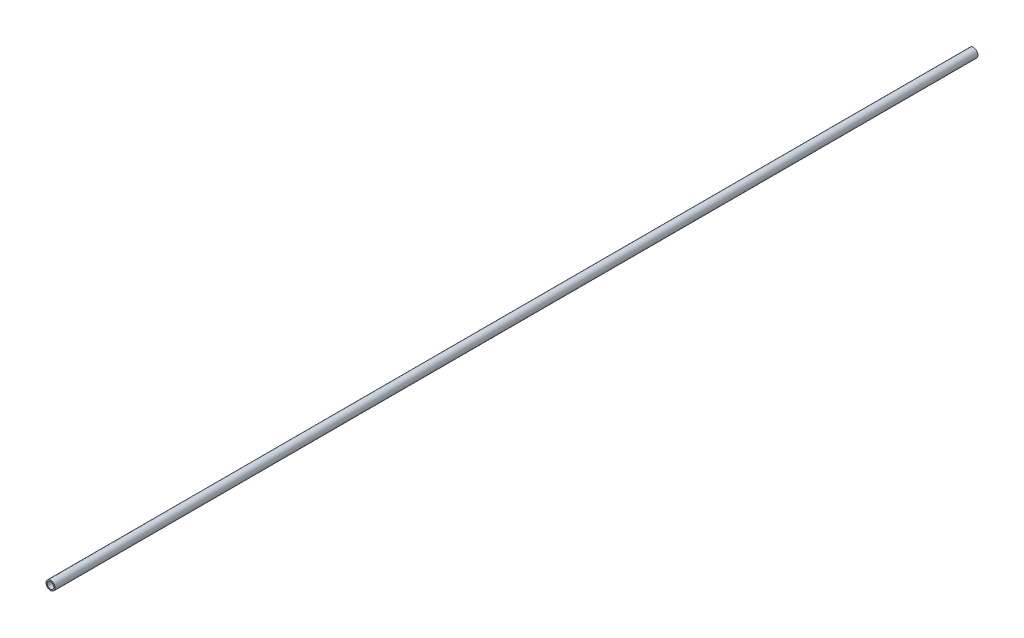
SolidWorks part; units mm, degrees
ref_plane "Front Plane" through (0, 0, 0) normal (0, 0, 1) x (1, 0, 0)
ref_plane "Top Plane" through (0, 0, 0) normal (0, 1, 0) x (1, 0, 0)
ref_plane "Right Plane" through (0, 0, 0) normal (1, 0, 0) x (0, 0, -1)
sketch "Sketch1" plane through (0, 0, 0) normal (0, 0, 1) x (1, 0, 0)
  circle A0 centre (0, 0) radius 4.7625
  circle A1 centre (0, 0) radius 3.5179
  dimension "D1" = 9.525
  dimension "D2" = 1.2446
extrude "Boss-Extrude1" add sketch "Sketch1" along normal blind 974.852
